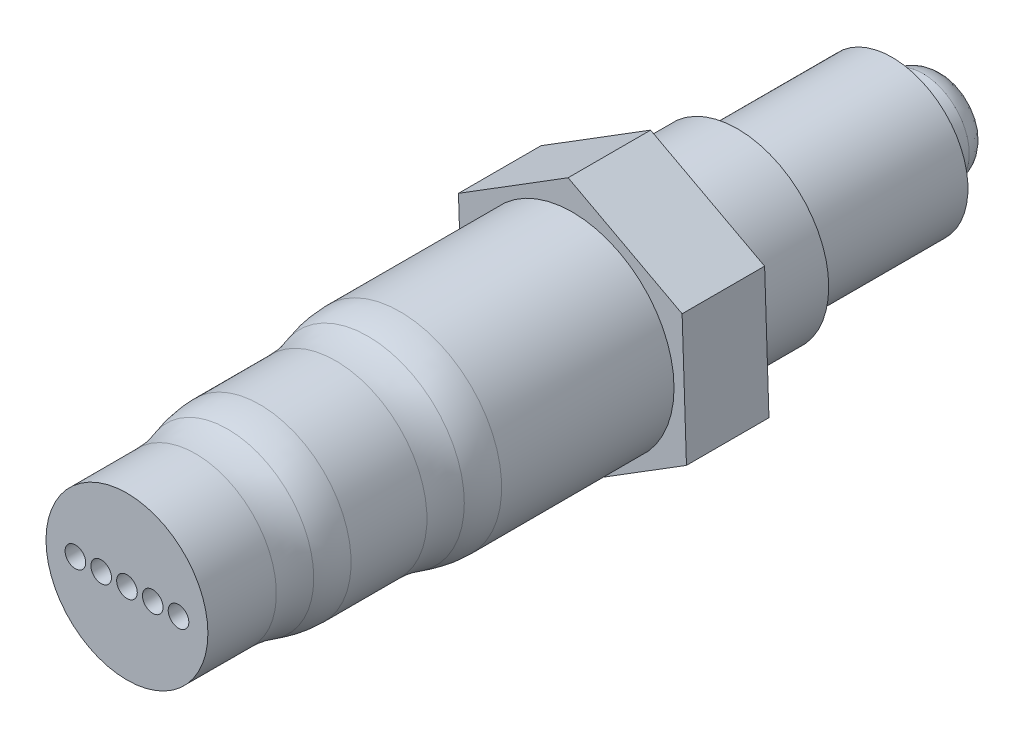
SolidWorks part; units mm, degrees
ref_plane "正面" through (0, 0, 0) normal (0, 0, 1) x (1, 0, 0)
ref_plane "平面" through (0, 0, 0) normal (0, 1, 0) x (1, 0, 0)
ref_plane "右側面" through (0, 0, 0) normal (1, 0, 0) x (0, 0, -1)
sketch "ｽｹｯﾁ1" plane through (0, 0, 0) normal (0, 0, 1) x (1, 0, 0)
  line L1 (11.0545, -5.8958) -> (10.6332, 6.6256)
  line L2 (10.6332, 6.6256) -> (-0.4213, 12.5214)
  line L3 (-0.4213, 12.5214) -> (-11.0545, 5.8958)
  line L4 (-11.0545, 5.8958) -> (-10.6332, -6.6256)
  line L5 (-10.6332, -6.6256) -> (0.4213, -12.5214)
  line L6 (0.4213, -12.5214) -> (11.0545, -5.8958)
  circle A0 centre (0, 0) radius 10.85 construction
  dimension "D1" = 21.7
extrude "ﾎﾞｽ - 押し出し1" add sketch "ｽｹｯﾁ1" along normal blind 8
sketch "ｽｹｯﾁ2" plane through (0, 0, 8) normal (0, 0, 1) x (1, 0, 0)
  circle A0 centre (0, 0) radius 9.85
  dimension "D1" = 19.7
extrude "ﾎﾞｽ - 押し出し2" add sketch "ｽｹｯﾁ2" along normal blind 18.6
sketch "ｽｹｯﾁ3" plane through (0, 0, 26.6) normal (0, 0, 1) x (1, 0, 0)
  circle A2 centre (0, 0) radius 8.85
  circle A3 centre (0, 0) radius 8.85
  dimension "D1" = 1
extrude "ﾎﾞｽ - 押し出し3" add sketch "ｽｹｯﾁ3" along normal blind 13.6
sketch "ｽｹｯﾁ4" plane through (0, 0, 40.2) normal (0, 0, 1) x (1, 0, 0)
  circle A2 centre (0, 0) radius 7.85
  circle A3 centre (0, 0) radius 7.85
  dimension "D1" = 1
extrude "ﾎﾞｽ - 押し出し4" add sketch "ｽｹｯﾁ4" along normal blind 11
sketch "ｽｹｯﾁ8" plane through (0, 0, 0) normal (0, 0, -1) x (-1, 0, 0)
  circle A0 centre (0, 0) radius 8.85
  dimension "D1" = 17.7
extrude "ﾎﾞｽ - 押し出し7" add sketch "ｽｹｯﾁ8" along normal blind 8
sketch "ｽｹｯﾁ9" plane through (0, 0, -8) normal (0, 0, -1) x (-1, 0, 0)
  circle A0 centre (0, 0) radius 7.35
  dimension "D1" = 14.7
extrude "ﾎﾞｽ - 押し出し8" add sketch "ｽｹｯﾁ9" along normal blind 15
sketch "ｽｹｯﾁ10" plane through (0, 0, -23) normal (0, 0, -1) x (-1, 0, 0)
  circle A0 centre (0, 0) radius 4.5
  dimension "D1" = 9
extrude "ﾎﾞｽ - 押し出し9" add sketch "ｽｹｯﾁ10" along normal blind 5
fillet "ﾌｨﾚｯﾄ1" radius 10 1 edges at (8.85, 0, 26.6)
fillet "ﾌｨﾚｯﾄ2" radius 10 1 edges at (9.85, 0, 26.6)
fillet "ﾌｨﾚｯﾄ3" radius 10 1 edges at (7.85, 0, 40.2)
fillet "ﾌｨﾚｯﾄ4" radius 10 1 edges at (8.85, 0, 40.2)
sketch "ｽｹｯﾁ11" plane through (0, 0, 0) normal (1, 0, 0) x (0, 0, -1)
  line L0 (25.979, 4.5) -> (28, 4.5)
  line L1 (28, 4.5) -> (23, 4.5) construction
  line L2 (28, 4.5) -> (28, 3.0124)
  line L3 (28, -4.5) -> (28, 4.5) construction
  line L4 (28, 0) -> (23, 0) construction
  line L5 (23, -7.35) -> (23, 7.35) construction
  spline S0 degree 3 poles (25.979, 4.5) (26.8242, 4.3783) (27.772, 3.9279) (28, 3.0124) knots 0 0 0 0 1 1 1 1
revolve "ｶｯﾄ - 回転1" cut sketch "ｽｹｯﾁ11" angle 360 about L4
sketch "ｽｹｯﾁ12" plane through (0, 0, 51.2) normal (0, 0, 1) x (1, 0, 0)
  line L0 (0, 0) -> (0, -5.4052) construction
  circle A0 centre (0, 0) radius 1
  circle A1 centre (2.5, 0) radius 1
  circle A2 centre (5, 0) radius 1
  circle A3 centre (-5, 0) radius 1
  circle A4 centre (-2.5, 0) radius 1
  dimension "D1" = 2
  dimension "D3" = 5
  dimension "D2" = 3
extrude "ｶｯﾄ - 押し出し1" cut sketch "ｽｹｯﾁ12" against normal blind 2
